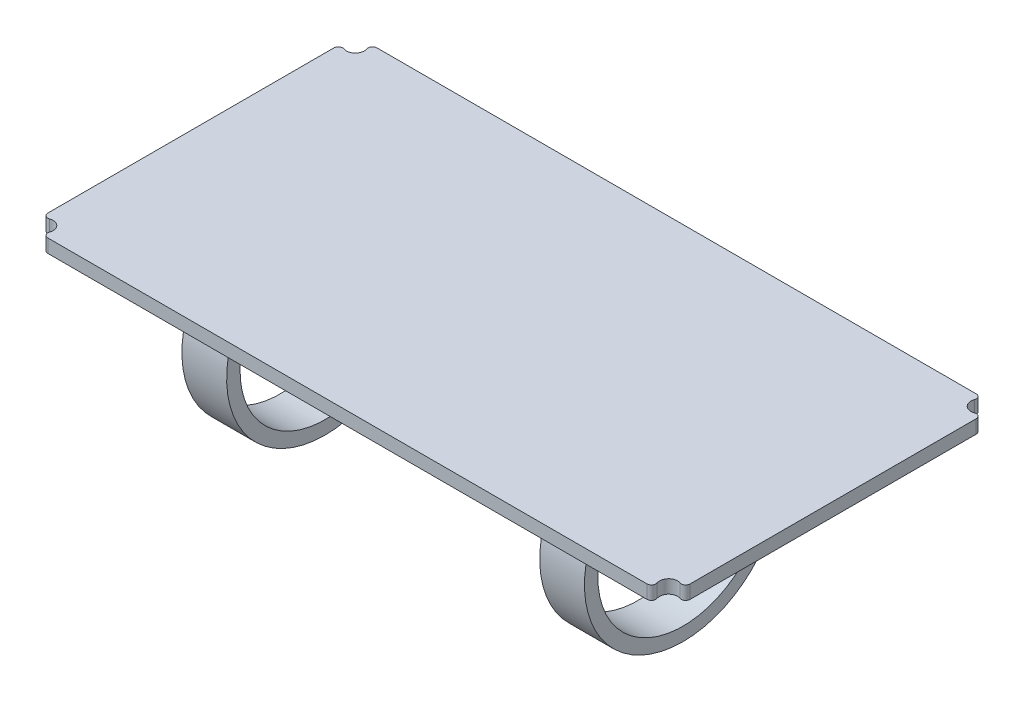
SolidWorks part; units mm, degrees
ref_plane "Front Plane" through (0, 0, 0) normal (0, 0, 1) x (1, 0, 0)
ref_plane "Top Plane" through (0, 0, 0) normal (0, 1, 0) x (1, 0, 0)
ref_plane "Right Plane" through (0, 0, 0) normal (1, 0, 0) x (0, 0, -1)
sketch "Sketch1" plane through (0, 0, 0) normal (0, 1, 0) x (1, 0, 0)
  line L1 (2.4142, 0) -> (69.3858, 0)
  line L2 (0, 2.4142) -> (0, 34.3858)
  line L3 (2.4142, 36.8) -> (69.3858, 36.8)
  line L4 (71.8, 2.4142) -> (71.8, 34.3858)
  arc A0 (0.6667, 34.8572) -> (1.9428, 36.1333) centre (1, 35.8) ccw
  arc A1 (1.9428, 0.6667) -> (0.6667, 1.9428) centre (1, 1) ccw
  arc A2 (71.1333, 1.9428) -> (69.8572, 0.6667) centre (70.8, 1) ccw
  arc A3 (69.8572, 36.1333) -> (71.1333, 34.8572) centre (70.8, 35.8) ccw
  arc A4 (69.8572, 36.1333) -> (69.3858, 36.8) centre (69.3858, 36.3) ccw
  arc A5 (71.8, 34.3858) -> (71.1333, 34.8572) centre (71.3, 34.3858) ccw
  arc A6 (71.1333, 1.9428) -> (71.8, 2.4142) centre (71.3, 2.4142) ccw
  arc A7 (69.8572, 0.6667) -> (69.3858, 0) centre (69.3858, 0.5) cw
  arc A8 (2.4142, 0) -> (1.9428, 0.6667) centre (2.4142, 0.5) cw
  arc A9 (0, 2.4142) -> (0.6667, 1.9428) centre (0.5, 2.4142) ccw
  arc A10 (2.4142, 36.8) -> (1.9428, 36.1333) centre (2.4142, 36.3) ccw
  arc A11 (0, 34.3858) -> (0.6667, 34.8572) centre (0.5, 34.3858) cw
  dimension "D3" = 1
  dimension "D7" = 1
  dimension "D2" = 0.5
  dimension "D4" = 1
  dimension "D5" = 1
  dimension "D6" = 1
  dimension "D8" = 1
  dimension "D9" = 1
  dimension "D10" = 1
extrude "Boss-Extrude1" add sketch "Sketch1" along normal blind 1.5
sketch "Sketch2" plane through (0, 0, 0) normal (0, -1, 0) x (1, 0, 0)
  line L0 (0, -18.4) -> (71.8, -18.4) construction
  line L1 (0, -34.3858) -> (0, -2.4142) construction
  line L2 (71.8, -2.4142) -> (71.8, -34.3858) construction
  line L3 (3, -12.6466) -> (68, -12.6466) construction
  dimension "D1" = 65
  dimension "D2" = 3
sketch "Sketch3" plane through (0, 0, 0) normal (-1, 0, 0) x (0, 0, 1)
  line L0 (-36.8, 1.5) -> (-36.8, 0) construction
  line L3 (-34.3858, 0) -> (-2.4142, 0) construction
  line L4 (-30.4991, 0) -> (-25.872, -3.6332)
  line L5 (-31.4255, -1.1798) -> (-26.7046, -4.8865)
  line L6 (-30.6566, -1.7835) -> (-26.7983, -4.8129) construction
  line L7 (-29.7303, -0.6037) -> (-25.872, -3.6332) construction
  line L8 (-30.4991, 0) -> (-12.8547, 0)
  line L9 (-32.3518, -2.3596) -> (-28.5765, -5.3239)
  line L10 (-31.4255, -1.1798) -> (-32.3518, -2.3596)
  line L11 (-33.8544, -1.1798) -> (-26.369, -7.0572) construction
  line L12 (-32.928, 0) -> (-25.4426, -5.8774) construction
  arc A0 (-26.7046, -4.8865) -> (-25.872, -3.6332) centre (-18.4, -9.5) ccw
  arc A2 (-28.5765, -5.3239) -> (-12.8547, 0) centre (-18.4, -9.5) ccw
  point P2 (-36.8, 0.75)
  point P13 (-7.4, -9.5)
  point P23 (-9.3151, -6.7225)
  line M1 (-34.3858, 0) -> (-2.4142, 0)
  dimension "D1" = 18.4
  dimension "D2" = 9.5
  dimension "D4" = 1.5
  dimension "D5" = 1.5
extrude "Boss-Extrude2" add sketch "Sketch3" against normal blind 5 from offset 10 contours L9 A2 L8 A0 L5 L10 | A0 L4 M1 region at (0, -1.1274, -25.7672) region at (0, -0.3229, -15.6274) offset against normal yes
extrude "Boss-Extrude3" add sketch "Sketch3<3>" against normal blind 5 from offset 50 contours A0 L4 M1 | L9 A2 L8 A0 L5 L10 region at (0, -1.1274, -25.7672) region at (0, -0.3229, -15.6274) offset against normal yes
sketch "Sketch3<3>" plane through (0, 0, 0) normal (-1, 0, 0) x (0, 0, 1) same geometry as "Sketch3"
fillet "Fillet1" radius 5 2 edges at (52.5, 0, -12.8547) (12.5, 0, -12.8547)
sketch "Sketch4" plane through (0, -17.1738, -13.4845) normal (0, -0.7865, -0.6176) x (1, 0, 0)
  line L0 (10, -19.2301) -> (15, -23.9882) construction
  line L1 (10, -23.9882) -> (10, -14.472) construction
  line L2 (15, -19.1882) -> (10, -23.9882) construction
  line L3 (50, -19.2301) -> (55, -23.9882) construction
  line L4 (50, -23.9882) -> (50, -14.472) construction
  line L5 (50, -23.9882) -> (55, -19.1882) construction
  circle A0 centre (12.5, -21.6092) radius 1.1
  circle A1 centre (52.5, -21.6092) radius 1.1
extrude "Cut-Extrude1" cut sketch "Sketch4" against normal blind 1.5
sketch "Sketch5" plane through (0, -17.1738, -13.4845) normal (0, -0.7865, -0.6176) x (1, 0, 0)
  circle A0 centre (12.5, -21.6092) radius 0.85
  circle A1 centre (52.5, -21.6092) radius 0.85
extrude "Cut-Extrude2" cut sketch "Sketch5" against normal blind 6
